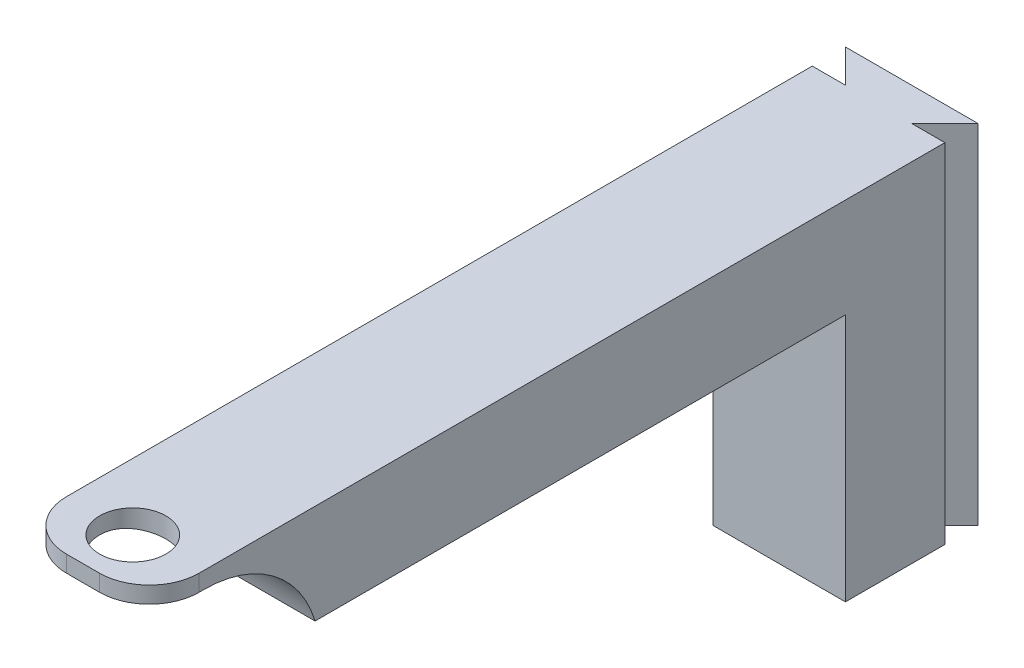
SolidWorks part; units mm, degrees
ref_plane "Front Plane" through (0, 0, 0) normal (0, 0, 1) x (1, 0, 0)
ref_plane "Top Plane" through (0, 0, 0) normal (0, 1, 0) x (1, 0, 0)
ref_plane "Right Plane" through (0, 0, 0) normal (1, 0, 0) x (0, 0, -1)
sketch "Sketch1" plane through (0, 0, 0) normal (0, 1, 0) x (1, 0, 0)
  line L1 (-4, -25) -> (4, -25)
  line L2 (-4, -25) -> (-4, 25)
  line L3 (-4, 25) -> (4, 25)
  line L4 (4, -25) -> (4, 25)
  line L5 (-4, -25) -> (4, 25) construction
  line L6 (-4, 25) -> (4, -25) construction
  point P0 (0, 0)
extrude "Boss-Extrude1" add sketch "Sketch1" along normal blind 6
sketch "Sketch2" plane through (0, 0, 0) normal (0, -1, 0) x (1, 0, 0)
  line L0 (-4, -25) -> (-4, 25) construction
  line L1 (4, 25) -> (-4, 25)
  line L2 (4, 25) -> (4, 15)
  line L3 (4, 15) -> (-4, 15)
  line L4 (-4, 25) -> (-4, 15)
extrude "Cut-Extrude2" cut sketch "Sketch2" against normal blind 5
sketch "Sketch3" plane through (0, 6, 0) normal (0, 1, 0) x (1, 0, 0)
  line L0 (0, -25) -> (0, -24) construction
  line L1 (-4, -25) -> (4, -25) construction
  line L2 (0, -24) -> (0, -22) construction
  circle A0 centre (0, -22) radius 2
extrude "Cut-Extrude3" cut sketch "Sketch3" against normal up to next
fillet "Fillet1" radius 3 2 edges at (4, 5.5, 25) (-4, 5.5, 25)
fillet "Fillet2" radius 7 1 edges at (0, 5, 15)
sketch "Sketch4" plane through (0, 0, 0) normal (0, -1, 0) x (-1, 0, 0)
  line L0 (4, 25) -> (4, -15) construction
  line L1 (-4, 25) -> (4, 25)
  line L2 (-4, 25) -> (-4, 17)
  line L3 (-4, 17) -> (4, 17)
  line L4 (4, 25) -> (4, 17)
extrude "Boss-Extrude2" add sketch "Sketch4" along normal blind 15
sketch "Sketch5" plane through (0, 6, 0) normal (0, 1, 0) x (1, 0, 0)
  line L0 (4, 25) -> (4, 23)
  line L1 (4, -22) -> (4, 25) construction
  line L2 (4, 23) -> (2, 23)
  line L3 (2, 23) -> (4, 25)
  line L4 (-4, 25) -> (-4, 23)
  line L5 (-4, 25) -> (-4, -22) construction
  line L6 (-4, 23) -> (-2, 23)
  line L7 (-2, 23) -> (-4, 25)
  point P14 (0, 0)
extrude "Cut-Extrude4" cut sketch "Sketch5" against normal up to next and the other way through all
